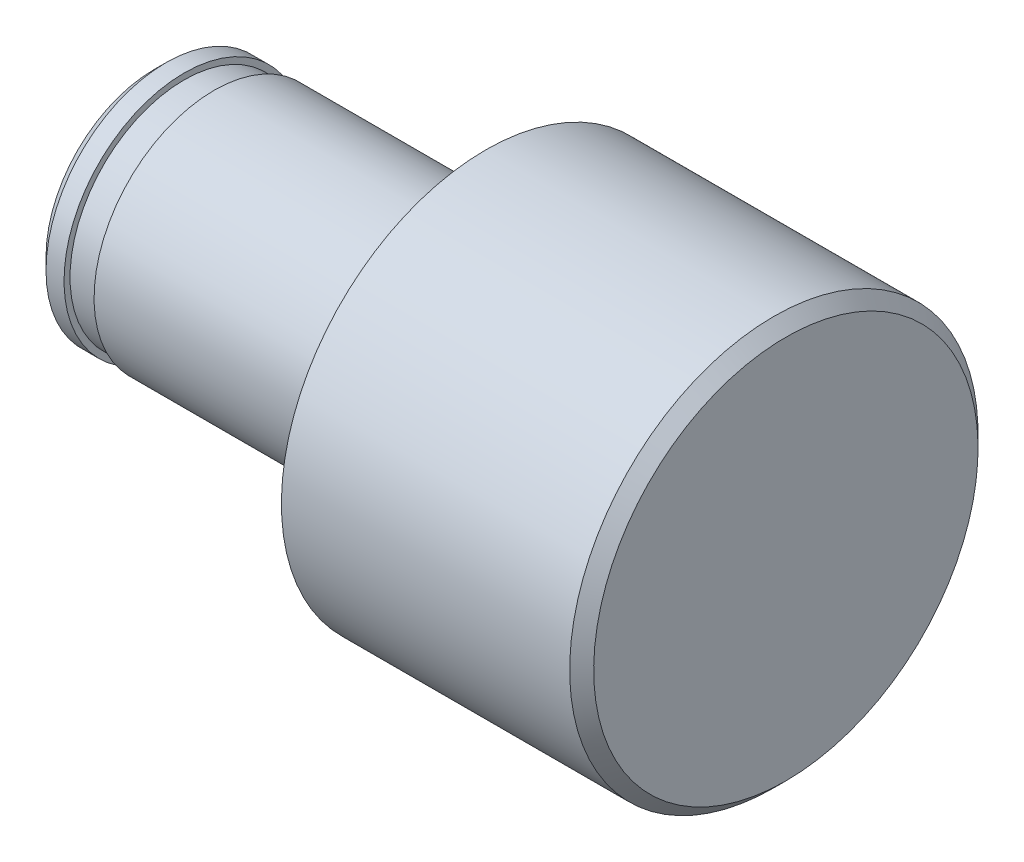
SolidWorks part; units mm, degrees
ref_plane "Vorne" through (0, 0, 0) normal (0, 0, 1) x (1, 0, 0)
ref_plane "Oben" through (0, 0, 0) normal (0, 1, 0) x (1, 0, 0)
ref_plane "Seite" through (0, 0, 0) normal (1, 0, 0) x (0, 0, -1)
sketch "Skizze2" plane through (0, 0, 0) normal (0, 0, 1) x (1, 0, 0)
  line L0 (3.9565, 0) -> (-6.5635, 0)
  line L1 (-6.5635, 0) -> (-6.5635, 2)
  line L2 (-6.5635, 2) -> (-6.0635, 2)
  line L3 (-6.0635, 2) -> (-6.0635, 1.9)
  line L4 (-6.0635, 1.9) -> (-5.5635, 1.9)
  line L5 (-5.5635, 1.9) -> (-5.5635, 2)
  line L6 (-5.5635, 2) -> (-1.0435, 2)
  line L7 (-1.0435, 2) -> (-1.0435, 3.4)
  line L8 (-1.0435, 3.4) -> (3.9565, 3.4)
  line L9 (3.9565, 3.4) -> (3.9565, 0)
  dimension "D1" = 0.5
  dimension "D2" = 0.1
  dimension "D3" = 0.5
  dimension "D4" = 4.52
  dimension "D5" = 5
  dimension "D6" = 3.4
  dimension "D7" = 2
revolve "Rotation1" add sketch "Skizze2" angle 360 about L0
chamfer "Fase1" distance 0.2 angle 45 2 edges at (3.9565, 3.4, 0) (-6.5635, 2, 0)
